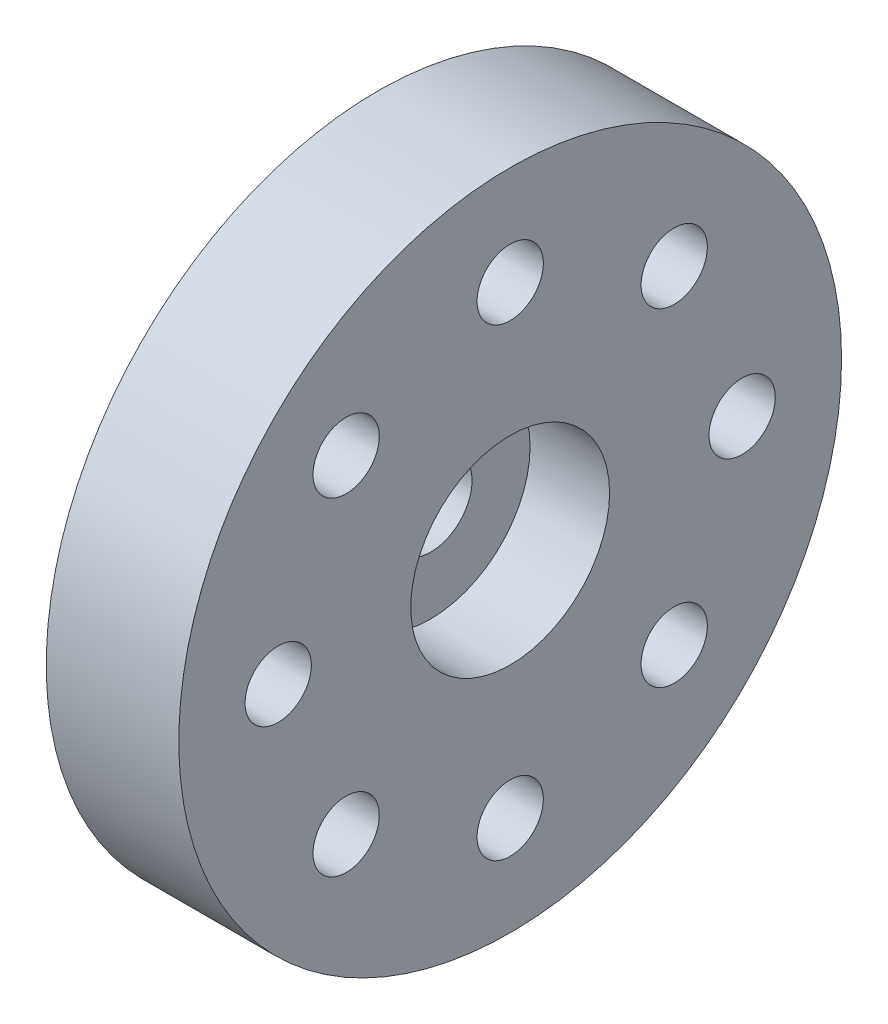
SolidWorks part; units mm, degrees
ref_plane "前视基准面" through (0, 0, 0) normal (0, 0, 1) x (1, 0, 0)
ref_plane "上视基准面" through (0, 0, 0) normal (0, 1, 0) x (1, 0, 0)
ref_plane "右视基准面" through (0, 0, 0) normal (1, 0, 0) x (0, 0, -1)
sketch "草图1" plane through (0, 0, 0) normal (1, 0, 0) x (0, 0, -1)
  circle A0 centre (0, 0) radius 10
  dimension "D1" = 20
extrude "凸台-拉伸1" add sketch "草图1" along normal blind 4
sketch "草图3" plane through (4, 0, 0) normal (1, 0, 0) x (0, 0, -1)
  circle A0 centre (0, 0) radius 3
  dimension "D1" = 6
extrude "切除-拉伸1" cut sketch "草图3" against normal through all
sketch "草图5" plane through (0, 0, 0) normal (-1, 0, 0) x (0, 0, 1)
  circle A0 centre (0, 7) radius 1
  dimension "D1" = 2
  dimension "D2" = 7
extrude "切除-拉伸2" cut sketch "草图5" against normal through all
ref_axis "基准轴1" through (0, 0, 0) along (1, 0, 0)
pattern_circular "阵列(圆周)1" count 8 over 360 about axis through (0, 0, 0) along (1, 0, 0) of "切除-拉伸2"
sketch "草图6" plane through (0, 0, 0) normal (-1, 0, 0) x (0, 0, 1)
  circle A0 centre (0, 0) radius 3.5
  circle A1 centre (0, 0) radius 3
  dimension "D1" = 7
extrude "凸台-拉伸3" add sketch "草图6" along normal blind 0.5
fillet "圆角3" radius 0.2 2 edges at (-0.5, 0, 3) (-0.5, 0, 3.5)
sketch "草图7" plane through (0, 0, 0) normal (-1, 0, 0) x (0, 0, 1)
  circle A0 centre (0, 0) radius 3.5
  circle A1 centre (0, 0) radius 1.25
  dimension "D1" = 2.5
  dimension "D2" = 7
extrude "凸台-拉伸4" add sketch "草图7" against normal blind 1.6
